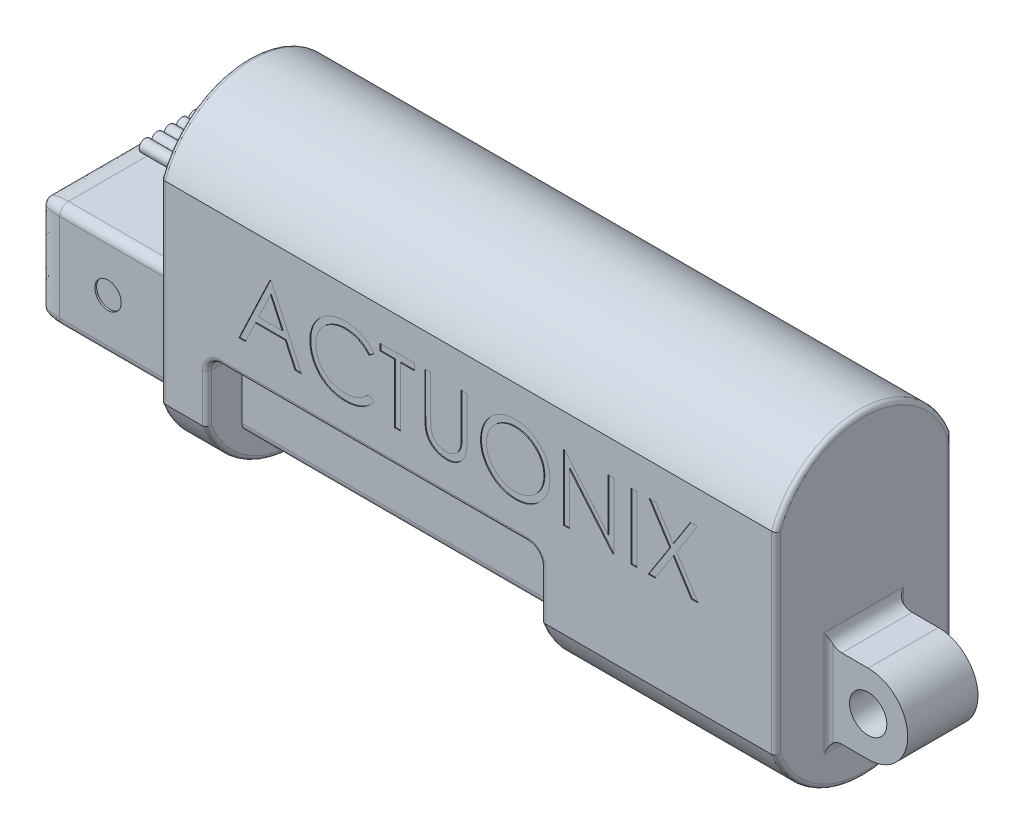
SolidWorks part; units mm, degrees
ref_plane "Front Plane" through (0, 0, 0) normal (0, 0, 1) x (1, 0, 0)
ref_plane "Top Plane" through (0, 0, 0) normal (0, 1, 0) x (1, 0, 0)
ref_plane "Right Plane" through (0, 0, 0) normal (1, 0, 0) x (0, 0, -1)
sketch "Sketch1" plane through (0, 0, 0) normal (0, 0, 1) x (1, 0, 0)
  line L0 (39.5, -12) -> (35, -12)
  line L1 (-35, 18) -> (35, 18)
  line L2 (-35, 18) -> (-35, -18)
  line L3 (-35, -18) -> (35, -18)
  line L4 (35, 18) -> (35, -3)
  line L5 (-35, 18) -> (35, -18) construction
  line L6 (-35, -18) -> (35, 18) construction
  line L7 (39.5, -3) -> (35, -3)
  line L8 (35, -12) -> (35, -18)
  circle A0 centre (39.5, -7.5) radius 2.125
  arc A1 (39.5, -12) -> (39.5, -3) centre (39.5, -7.5) ccw
  point P0 (0, 0)
  point P9 (44, -7.5)
  dimension "D3" = 4.25
  dimension "D5" = 4.5
  dimension "D1" = 70
  dimension "D2" = 36
  dimension "D4" = 10.5
  dimension "D6" = 4.5
extrude "Boss-Extrude1" add sketch "Sketch1" along normal mid plane 20
sketch "Sketch2" plane through (0, 18, 0) normal (0, 1, 0) x (1, 0, 0)
  line L1 (35, -10) -> (44, -10)
  line L2 (35, -10) -> (35, 10)
  line L3 (35, 10) -> (44, 10)
  line L4 (44, -10) -> (44, 10)
  line L5 (35, -4) -> (44, -4)
  line L6 (35, -4) -> (35, 4)
  line L7 (35, 4) -> (44, 4)
  line L8 (44, -4) -> (44, 4)
  line L9 (35, -4) -> (44, 4) construction
  line L10 (35, 4) -> (44, -4) construction
  point P6 (39.5, 0)
  point P11 (35, 0)
  line M12 (35, -10) -> (35, 10)
  dimension "D1" = 8
extrude "Cut-Extrude1" cut sketch "Sketch2" against normal through all contours L5 L1 L4 M12 | L7 L4 L3 M12 region at (39.5, 18, 7) region at (39.5, 18, -7)
sketch "Sketch3" plane through (0, 0, 10) normal (0, 0, 1) x (1, 0, 0)
  line L1 (-35, -18) -> (35, -18) construction
  line L2 (-29.75, -18) -> (-29.75, -13.5)
  line L3 (-29.75, -13.5) -> (8.25, -13.5)
  line L5 (8.25, -13.5) -> (8.25, -18)
  line L6 (-29.75, -18) -> (8.25, -18)
  line L7 (-35, 18) -> (-35, -18) construction
  dimension "D1" = 5.25
  dimension "D2" = 38
  dimension "D3" = 4.5
extrude "Cut-Extrude2" cut sketch "Sketch3" against normal through all contours L6 L5 L3 L2
sketch "Sketch4" plane through (0, -13.5, 0) normal (0, -1, 0) x (1, 0, 0)
  line L0 (8.25, -10) -> (8.25, 10) construction
  line L1 (-29.75, -10) -> (8.25, -10)
  line L2 (-29.75, -10) -> (-29.75, -6)
  line L3 (-29.75, -6) -> (8.25, -6)
  line L4 (8.25, -10) -> (8.25, -6)
  line L5 (-29.75, 0) -> (8.25, 0) construction
  line L6 (-29.75, 10) -> (8.25, 10)
  line L7 (-29.75, 10) -> (-29.75, 6)
  line L8 (-29.75, 6) -> (8.25, 6)
  line L9 (8.25, 10) -> (8.25, 6)
  line L10 (-29.75, -10) -> (-29.75, 10) construction
  dimension "D1" = 12
extrude "Cut-Extrude3" cut sketch "Sketch4" against normal blind 9.5
sketch "Sketch5" plane through (-35, 0, 0) normal (-1, 0, 0) x (0, 0, 1)
  line L0 (-6, -13.5) -> (6, -13.5) construction
  line L1 (-6, -13.5) -> (6, -13.5) construction
  line L2 (-6, -4) -> (-6, -13.5) construction
  line L3 (6, -4) -> (6, -13.5) construction
  line L4 (-6, -4) -> (-6, -13.5) construction
  line L5 (6, -4) -> (6, -13.5) construction
  line L6 (-6, -4) -> (-6, -1.5) construction
  line L7 (-6, -1.5) -> (6, -1.5) construction
  line L8 (6, -1.5) -> (6, -4) construction
  line L9 (-5.625, 3.375) -> (1.125, 3.375) construction
  line L10 (-5.625, 5.25) -> (1.125, 5.25)
  line L11 (-5.625, 1.5) -> (1.125, 1.5)
  line L12 (0, 18) -> (0, -1.5) construction
  line L13 (10, 18) -> (-10, 18) construction
  arc A0 (-5.625, 5.25) -> (-5.625, 1.5) centre (-5.625, 3.375) ccw
  arc A1 (1.125, 1.5) -> (1.125, 5.25) centre (1.125, 3.375) ccw
  point P8 (-2.25, 3.375)
  point P17 (3, 3.375)
  point P18 (-7.5, 3.375)
  dimension "D1" = 12
  dimension "D2" = 3
  dimension "D3" = 3
  dimension "D4" = 3.75
  dimension "D5" = 10.5
sketch "Sketch6" plane through (35, 0, 0) normal (1, 0, 0) x (0, 0, -1)
  line L0 (0, 18) -> (0, -3.0686) construction
  line L1 (-10, 18) -> (10, 18) construction
  line L2 (-10, 18) -> (-10, 11) construction
  line L3 (-10, -18) -> (-10, 18) construction
  line L4 (10, -18) -> (10, 18) construction
  arc A0 (-10, 11) -> (10, 11) centre (0, 7.3571) cw
  line M5 (10, 18) -> (-10, 18)
  line M6 (-10, 18) -> (-10, -18)
  line M8 (10, -18) -> (10, 18)
  dimension "D1" = 7
extrude "Cut-Extrude4" cut sketch "Sketch6" against normal through all and the other way through all contours A0 M6 M5 | A0 M5 M8 region at (35, 16.112, 7.6911) region at (35, 16.112, -7.6911)
sketch "Sketch7" plane through (35, 0, 0) normal (1, 0, 0) x (0, 0, -1)
  line L0 (0, 0) -> (-10, 0) construction
  line L1 (-10, -18) -> (-10, 11) construction
  line L2 (10, -18) -> (10, 11) construction
  line L4 (-10, -11) -> (-10, -18)
  line L5 (-10, -18) -> (10, -18)
  line L6 (10, -18) -> (10, -11)
  arc A0 (10, 11) -> (-10, 11) centre (0, 7.3571) ccw construction
  arc A2 (10, -11) -> (-10, -11) centre (0, -7.3571) cw
  line M5 (10, -18) -> (10, 11)
  line M7 (-10, 11) -> (-10, -18)
  line M8 (-10, -18) -> (10, -18)
extrude "Cut-Extrude5" cut sketch "Sketch7" against normal through all contours A2 M8 M7 | A2 L5 M5 region at (35, -16.112, 7.6911) region at (35, -16.112, -7.6911)
extrude "Boss-Extrude2" add sketch "Sketch5" along normal blind 4.31 separate body
sketch "Sketch8" plane through (-39.31, 0, 0) normal (-1, 0, 0) x (0, 0, 1)
  circle A0 centre (-5.625, 3.375) radius 0.675
  circle A1 centre (-4.225, 3.375) radius 0.675
  circle A2 centre (-2.825, 3.375) radius 0.675
  circle A3 centre (-1.425, 3.375) radius 0.675
  circle A4 centre (-0.025, 3.375) radius 0.675
  dimension "D1" = 1.35
  dimension "D2" = 1.4
  dimension "D3" = 1.4
  dimension "D4" = 1.4
  dimension "D5" = 1.4
extrude "Boss-Extrude3" add sketch "Sketch8" along normal blind 7.5 separate body
sketch "Sketch9" plane through (-35, 0, 0) normal (-1, 0, 0) x (0, 0, 1)
  line L0 (-6, -4) -> (-6, -1.5) construction
  line L1 (-6, -4) -> (-6, -13.5) construction
  line L2 (-6, -13.5) -> (6, -13.5) construction
  line L3 (6, -4) -> (6, -13.5) construction
  line L4 (6, -1.5) -> (6, -4) construction
  line L5 (-6, -1.5) -> (6, -1.5) construction
  line L6 (-6, -4) -> (-6, -2.5)
  line L7 (-6, -4) -> (-6, -12.5)
  line L8 (-5, -13.5) -> (5, -13.5)
  line L9 (6, -4) -> (6, -12.5)
  line L10 (6, -2.5) -> (6, -4)
  line L11 (-5, -1.5) -> (5, -1.5)
  arc A0 (-6, -12.5) -> (-5, -13.5) centre (-5, -12.5) ccw
  arc A1 (5, -13.5) -> (6, -12.5) centre (5, -12.5) ccw
  arc A2 (6, -2.5) -> (5, -1.5) centre (5, -2.5) ccw
  arc A3 (-6, -2.5) -> (-5, -1.5) centre (-5, -2.5) cw
  dimension "D1" = 1
extrude "Boss-Extrude4" add sketch "Sketch9" along normal blind 17.5 separate body
sketch "Sketch10" plane through (-52.5, 0, 0) normal (-1, 0, 0) x (0, 0, 1)
  line L0 (0, -1.5) -> (0, -13.5) construction
  line L1 (5, -1.5) -> (-5, -1.5) construction
  line L2 (-5, -13.5) -> (5, -13.5) construction
  circle A0 centre (0, -7.5) radius 4.5
  dimension "D1" = 9
extrude "Cut-Extrude6" cut sketch "Sketch10" against normal blind 50
sketch "Sketch12" plane through (0, 0, 10) normal (0, 0, 1) x (1, 0, 0)
  line L0 (-35, -0.25) -> (35, -0.25) construction
  line L1 (-35, 11) -> (-35, -11) construction
  line L2 (35, -11) -> (35, 11) construction
  line L3 (8.25, -4) -> (-29.75, -4) construction
  text T0 "ACTUONIX" font "Century Gothic" height 7.5
  dimension "D1" = 3.75
extrude "Cut-Extrude7" cut sketch "Sketch12" against normal blind 0.1
sketch "Sketch13" plane through (0, 0, -10) normal (0, 0, -1) x (-1, 0, 0)
  line L0 (35, -0.25) -> (-35, -0.25) construction
  line L1 (35, -0.25) -> (-35, -0.25) construction
  line L2 (-35, 7.25) -> (35, 7.25) construction
  line L3 (-35, -11) -> (-35, 11) construction
  line L4 (35, 11) -> (35, -11) construction
  text T0 "ACTUONIX" font "Century Gothic" height 7.5
  dimension "D1" = 7.5
extrude "Cut-Extrude8" cut sketch "Sketch13" against normal blind 0.1
fillet "Fillet1" radius 2 8 edges at (-52.5, -13.5, 0) (-52.5, -7.5, 6) (-52.5, -1.5, 0) (-52.5, -7.5, -6) (-52.5, -1.7929, 5.7071) (-52.5, -13.2071, 5.7071) (-52.5, -1.7929, -5.7071) (-52.5, -13.2071, -5.7071) second distance 0.5 first distance on face at (-43.75, -13.5, 0) first distance on face at (-43.75, -7.5, 6) first distance on face at (-43.75, -1.5, 0) first distance on face at (-43.75, -7.5, -6) first distance on face at (-43.75, -1.8964, 5.6036) first distance on face at (-43.75, -13.1036, 5.6036) first distance on face at (-43.75, -1.8964, -5.6036) first distance on face at (-43.75, -13.1036, -5.6036)
sketch "Sketch14" plane through (0, 0, 6) normal (0, 0, 1) x (1, 0, 0)
  line L0 (-50.5, -7.5) -> (-35, -7.5) construction
  line L1 (-50.5, -2.5) -> (-50.5, -12.5) construction
  line L2 (-35, -12.5) -> (-35, -2.5) construction
  circle A0 centre (-45, -7.5) radius 1.5
  dimension "D1" = 3
  dimension "D2" = 5.5
extrude "Cut-Extrude9" cut sketch "Sketch14" against normal blind 0.2
sketch "Sketch15" plane through (0, 0, -6) normal (0, 0, -1) x (-1, 0, 0)
  circle A1 centre (45, -7.5) radius 1.5
  circle A2 centre (45, -7.5) radius 1.5
  dimension "D1" = 0
extrude "Cut-Extrude10" cut sketch "Sketch15" against normal blind 0.2
fillet "Fillet2" radius 1.5 4 edges at (-29.75, -4, 8) (-29.75, -4, -8) (8.25, -4, -8) (8.25, -4, 8)
fillet "Fillet3" radius 1.5 2 edges at (35, -3, 0) (35, -12, 0)
fillet "Fillet4" radius 0.5 2 edges at (35, -7.5, 4) (35, -7.5, -4)
fillet "Fillet5" radius 1 2 edges at (-10.75, -13.5, -6) (-10.75, -13.5, 6)
fillet "Fillet6" radius 0.5 20 edges at (-29.75, -8.25, 10) (-29.3107, -4.4393, 10) (-10.75, -4, 10) (7.8107, -4.4393, 10) (8.25, -8.25, 10) (8.25, -18, 0) (7.8107, -4.4393, -10) (8.25, -8.25, -10) (-10.75, -4, -10) (-29.3107, -4.4393, -10) (-29.75, -8.25, -10) (-29.75, -18, 0) (35, 0, 10) (35, 18, 0) (35, 0, -10) (35, -18, 0) (-35, -18, 0) (-35, 0, -10) (-35, 18, 0) (-35, 0, 10)
